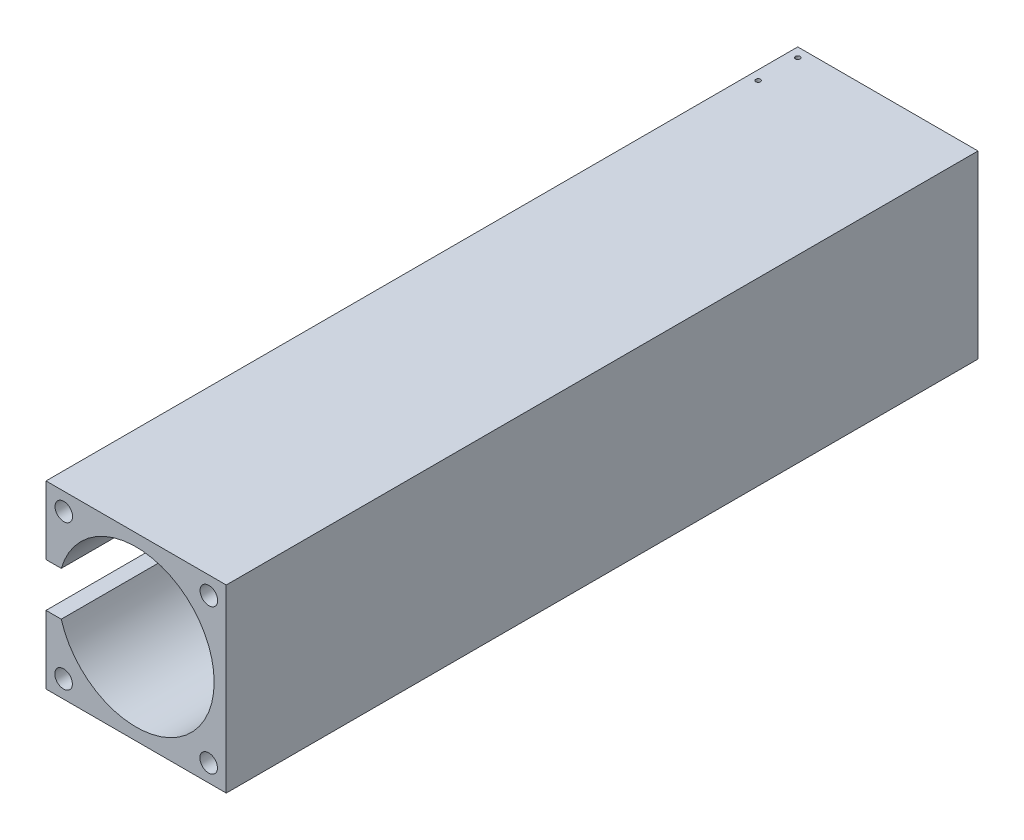
SolidWorks part; units mm, degrees
ref_plane "前基準面" through (0, 0, 0) normal (0, 0, 1) x (1, 0, 0)
ref_plane "上基準面" through (0, 0, 0) normal (0, 1, 0) x (1, 0, 0)
ref_plane "右基準面" through (0, 0, 0) normal (1, 0, 0) x (0, 0, -1)
ref_axis "基準軸1" through (0, -55, 0) along (0, 1, 0)
ref_axis "基準軸2" through (-88.99, 0, 0) along (1, 0, 0)
ref_axis "基準軸3" through (0, 0, 55) along (0, 0, -1)
sketch "草圖1" plane through (0, 0, 0) normal (0, 0, 1) x (1, 0, 0)
  line L0 (0, -55) -> (0, 55) construction
  line L1 (-41, -41) -> (41, -41)
  line L2 (-41, -41) -> (-41, 41)
  line L3 (-41, 41) -> (41, 41)
  line L4 (41, -41) -> (41, 41)
  line L5 (55, 0) -> (-55, 0) construction
  circle A0 centre (0, 0) radius 35.5
  point P7 (0, -41)
  point P10 (41, 0)
  dimension "D1" = 71
  dimension "D2" = 82
  dimension "D3" = 82
extrude "填料-伸長1" add sketch "草圖1" along normal blind 315
sketch "草圖2" plane through (0, 0, 0) normal (0, 0, -1) x (-1, 0, 0)
  line L1 (-41, 41) -> (41, 41)
  line L2 (-41, 41) -> (-41, -41)
  line L3 (-41, -41) -> (41, -41)
  line L4 (41, 41) -> (41, -41)
extrude "填料-伸長2" add sketch "草圖2" along normal blind 27
ref_plane "平面1" through (0, 0, -13.5) normal (0, 0, -1) x (-1, 0, 0)
sketch "草圖3" plane through (0, 0, 315) normal (0, 0, 1) x (1, 0, 0)
  line L0 (-41, 41) -> (-41, -41) construction
  line L1 (-41, 10) -> (-33, 10)
  line L2 (-41, 10) -> (-41, -10)
  line L3 (-41, -10) -> (-33, -10)
  line L4 (-33, 10) -> (-33, -10)
  line L6 (45.1, 0) -> (-45.1, 0) construction
  point P6 (-33, 0)
  dimension "D1" = 8
  dimension "D2" = 20
extrude "除料-伸長1" cut sketch "草圖3" against normal up to surface (315 mm away) up to face at (35.5, 0, 0)
sketch "草圖4" plane through (0, 0, 315) normal (0, 0, 1) x (1, 0, 0)
  line L1 (41, 41) -> (-41, 41) construction
  line L2 (-41, 41) -> (-41, 10) construction
  line L3 (-41, -41) -> (41, -41) construction
  line L4 (-41, -10) -> (-41, -41) construction
  circle A0 centre (-32.9, 33) radius 4
  circle A1 centre (33.1, 32.9) radius 4
  circle A2 centre (33, -33.1) radius 4
  circle A3 centre (-33, -33) radius 4
  point P15 (0.05, -0.05)
  dimension "D1" = 8
  dimension "D5" = 8
  dimension "D2" = 8
  dimension "D3" = 8.1
  dimension "D6" = 8
  dimension "D4" = 4
extrude "除料-伸長2" cut sketch "草圖4" against normal blind 20
fillet "圓角2" radius 3 1 edges at (-28.9, 33, 295)
fillet "圓角3" radius 3 1 edges at (37.1, 32.9, 295)
fillet "圓角4" radius 3 1 edges at (-29, -33, 295)
fillet "圓角5" radius 3 1 edges at (37, -33.1, 295)
sketch "草圖5" plane through (0, 41, 0) normal (0, 1, 0) x (1, 0, 0)
  line L0 (-41, -315) -> (-41, 27) construction
  line L4 (-41, 27) -> (41, 27) construction
  circle A2 centre (-36.75, 22.75) radius 1.05
  circle A3 centre (-36.75, 4.75) radius 1.05
  point P8 (-36.7138, 25.7547)
  dimension "D1" = 18
  dimension "D2" = 2.1
  dimension "D3" = 2.1
  dimension "D4" = 4.25
  dimension "D5" = 4.25
  dimension "D6" = 4.25
extrude "除料-伸長3" cut sketch "草圖5" against normal blind 10
ref_plane "平面2" through (0, 35, 0) normal (0, 1, 0) x (1, 0, 0)
sketch "草圖6" plane through (0, 35, 0) normal (0, 1, 0) x (1, 0, 0)
  circle A0 centre (-36.75, 22.75) radius 1.05
  circle A1 centre (-36.75, 4.75) radius 1.05
  dimension "D1" = 2.1
  dimension "D2" = 2.1
extrude "填料-伸長3" add sketch "草圖6" along normal blind 0.2
